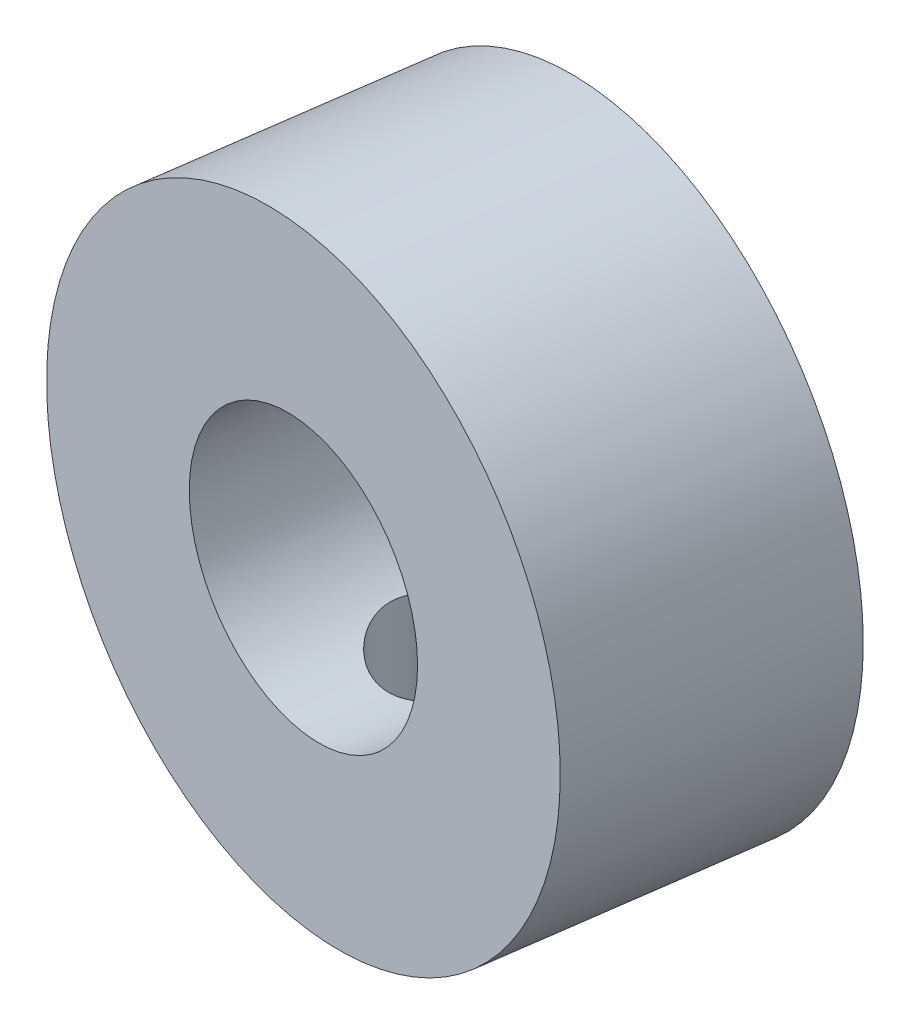
SolidWorks part; units mm, degrees
ref_plane "Front Plane" through (0, 0, 0) normal (0, 0, 1) x (1, 0, 0)
ref_plane "Top Plane" through (0, 0, 0) normal (0, 1, 0) x (1, 0, 0)
ref_plane "Right Plane" through (0, 0, 0) normal (1, 0, 0) x (0, 0, -1)
sketch "Sketch1" plane through (-29.9585, -0.0055, 37.9225) normal (0.9894, -0.0409, 0.1391) x (0.1393, 0, -0.9903)
  line L0 (22.0768, -11.1359) -> (73.3766, -11.1359) construction
  line L1 (50.2159, -3.9922) -> (56.5659, -3.9922) construction
  line L2 (50.2159, -3.9922) -> (50.2159, -18.2797) construction
  line L3 (50.2159, -18.2797) -> (56.5659, -18.2797) construction
  line L4 (56.5659, -3.9922) -> (56.5659, -18.2797) construction
  line L5 (50.2159, -11.1359) -> (56.5659, -11.1359)
  line L6 (50.2159, -3.9922) -> (56.5659, -3.9922)
  line L7 (50.2159, -14.3109) -> (50.2159, -18.2797)
  line L8 (50.2159, -18.2797) -> (56.5659, -18.2797)
  line L9 (56.5659, -14.3109) -> (56.5659, -18.2797)
  line L10 (38.8875, -14.3109) -> (56.5659, -14.3109) construction
  line L11 (50.2159, -14.3109) -> (56.5659, -14.3109)
revolve "Revolve1" add sketch "Sketch1" angle 360 about L5 region at (-23.1839, -16.2871, -15.0411)
ref_plane "Plane1" through (0, -18.2758, 0) normal (0, -1, 0) x (-1, 0, 0)
sketch "Sketch2" plane through (0, -18.2758, 0) normal (0, -1, 0) x (-1, 0, 0)
  line L0 (23.7064, 11.9083) -> (22.8221, 18.1964) construction
  line L1 (23.7064, 11.9083) -> (22.8221, 18.1964)
  point P2 (23.2643, 15.0524)
hole_wizard "#6-32 Tapped Hole1" positions "Sketch4" profile "Sketch5" tap size "#6-32" standard "ANSI Inch"
sketch "Sketch4" plane through (0, -18.2758, 0) normal (0, -1, 0) x (-1, 0, 0)
  point P0 (23.2643, 15.0524)
sketch "Sketch5" plane through (-23.2643, -18.2758, -15.0524) normal (1, 0, 0) x (0, 0, -1)
  line L0 (0, 0) -> (0, 7.1627)
  line L1 (0, 7.1627) -> (1.3525, 6.35)
  line L2 (1.3525, 6.35) -> (1.3525, 0)
  line L5 (1.3525, 0) -> (0, 0)
  line L10 (0, 7.1627) -> (-1.3526, 6.35) construction
  line L11 (0, -6.35) -> (0, 107.95) construction
  dimension "Tap Drill Dia." = 2.7051
  dimension "Tap Drill Depth" = 6.35
  dimension "Drill Angle" = 118
cosmetic thread "Hole Thread1" parameters "D1"=3.4775, "D2"=3.5052
